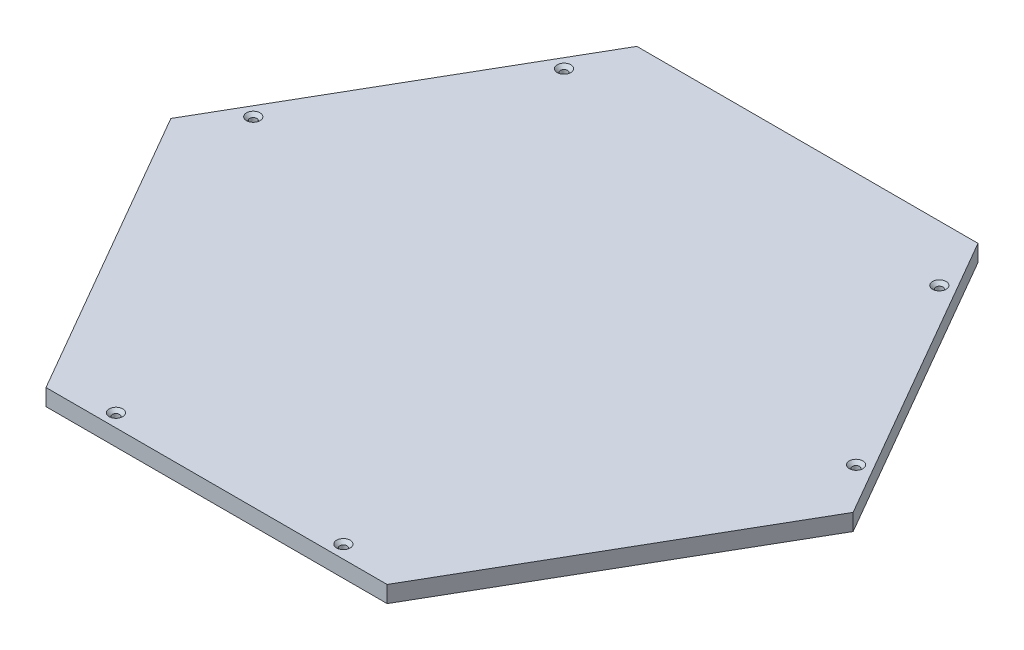
SolidWorks part; units mm, degrees
ref_plane "Front Plane" through (0, 0, 0) normal (0, 0, 1) x (1, 0, 0)
ref_plane "Top Plane" through (0, 0, 0) normal (0, 1, 0) x (1, 0, 0)
ref_plane "Right Plane" through (0, 0, 0) normal (1, 0, 0) x (0, 0, -1)
sketch "Sketch1" plane through (0, 484.3134, 0) normal (0, 1, 0) x (1, 0, 0)
  line L0 (745.0585, -1508.4785) -> (535.0585, -1872.2091) construction
  line L1 (1096.7234, -1803.3391) -> (966.2477, -1577.3485)
  line L2 (966.2477, -1577.3485) -> (705.2963, -1577.3485)
  line L3 (705.2963, -1577.3485) -> (574.8206, -1803.3391)
  line L4 (574.8206, -1803.3391) -> (705.2963, -2029.3296)
  line L5 (705.2963, -2029.3296) -> (966.2477, -2029.3296)
  line L6 (966.2477, -2029.3296) -> (1096.7234, -1803.3391)
  line L7 (1136.4856, -1872.2091) -> (926.4856, -1508.4785) construction
  line L8 (625.772, -2029.3296) -> (1045.772, -2029.3296) construction
  circle A0 centre (835.772, -1803.3391) radius 225.9905 construction
extrude "Boss-Extrude1" add sketch "Sketch1" along normal blind 12.7
sketch "Sketch2" plane through (0, 497.0134, 0) normal (0, 1, 0) x (1, 0, 0)
  line L0 (835.772, -1577.3485) -> (835.772, -1724.1646)
  line L1 (966.2477, -1577.3485) -> (705.2963, -1577.3485) construction
  line L2 (1031.4856, -1916.3343) -> (962.1709, -1876.3155)
  line L3 (966.2477, -2029.3296) -> (1096.7234, -1803.3391) construction
  line L4 (640.0585, -1916.3343) -> (702.4259, -1880.3243)
  line L5 (574.8206, -1803.3391) -> (705.2963, -2029.3296) construction
  line L6 (640.0585, -1690.3438) -> (648.7187, -1695.3438)
  line L7 (705.2963, -1577.3485) -> (574.8206, -1803.3391) construction
  line L8 (605.2187, -1770.688) -> (692.2187, -1619.9996)
  line L9 (574.8206, -1803.3391) -> (596.5496, -1815.8843)
  line L10 (1066.3253, -1770.688) -> (979.3253, -1619.9996)
  line L11 (1031.4856, -1690.3438) -> (1022.8253, -1695.3438)
  line L12 (748.7776, -2019.3237) -> (922.7776, -2019.3144)
  line L13 (835.7781, -2029.3191) -> (835.7776, -2019.3191)
  point P30 (605.2187, -1770.688)
  point P31 (692.2187, -1619.9996)
  point P32 (979.3253, -1619.9996)
  point P33 (1066.3253, -1770.688)
  point P34 (922.7776, -2019.3144)
  point P35 (748.7776, -2019.3237)
  dimension "D1" = 174
  dimension "D2" = 10
hole_wizard "CSK for M5 Flat Head Machine Screw1" positions "Sketch6" profile "Sketch5" countersink size "M5" standard "ANSI Metric" end condition up to next
sketch "Sketch6" plane through (0, 497.0134, 0) normal (0, 1, 0) x (1, 0, 0)
  line L0 (640.0585, -1690.3438) -> (648.7187, -1695.3438) construction
  line L1 (640.0585, -1916.3343) -> (702.4259, -1880.3243) construction
  line L2 (1031.4856, -1916.3343) -> (962.1709, -1876.3155) construction
  line L3 (835.772, -1577.3485) -> (835.772, -1724.1646) construction
  line L4 (835.7781, -2029.3191) -> (835.7776, -2019.3191) construction
  line L5 (748.7776, -2019.3237) -> (922.7776, -2019.3144) construction
  line L6 (1031.4856, -1690.3438) -> (1022.8253, -1695.3438) construction
  line L7 (1066.3253, -1770.688) -> (979.3253, -1619.9996) construction
  line L8 (574.8206, -1803.3391) -> (596.5496, -1815.8843) construction
  line L9 (605.2187, -1770.688) -> (692.2187, -1619.9996) construction
  line L10 (640.0585, -1690.3438) -> (648.7187, -1695.3438) construction
  line L11 (640.0585, -1916.3343) -> (702.4259, -1880.3243) construction
  line L12 (1031.4856, -1916.3343) -> (962.1709, -1876.3155) construction
  line L13 (835.772, -1577.3485) -> (835.772, -1724.1646) construction
  line L14 (835.7781, -2029.3191) -> (835.7776, -2019.3191) construction
  line L15 (748.7776, -2019.3237) -> (922.7776, -2019.3144) construction
  line L16 (1031.4856, -1690.3438) -> (1022.8253, -1695.3438) construction
  line L17 (1066.3253, -1770.688) -> (979.3253, -1619.9996) construction
  line L18 (574.8206, -1803.3391) -> (596.5496, -1815.8843) construction
  line L19 (605.2187, -1770.688) -> (692.2187, -1619.9996) construction
  point P0 (605.2187, -1770.688)
  point P2 (692.2187, -1619.9996)
  point P4 (979.3253, -1619.9996)
  point P6 (1066.3253, -1770.688)
  point P8 (748.7776, -2019.3237)
  point P10 (922.7776, -2019.3144)
sketch "Sketch5" plane through (605.2187, 497.0134, 1770.688) normal (1, 0, 0) x (0, 0, 1)
  line L0 (0, 0) -> (0, 12.7)
  line L1 (0, 12.7) -> (2.75, 12.7)
  line L2 (2.75, 12.7) -> (2.75, 2.45)
  line L3 (2.75, 2.45) -> (5.2, 0)
  line L5 (5.2, 0) -> (0, 0)
  line L6 (-2.75, 2.45) -> (-5.2, 0) construction
  line L11 (0, -6.35) -> (0, 107.95) construction
  dimension "Thru Hole Dia." = 5.5
  dimension "Thru Hole Depth" = 12.7
  dimension "Near C'Sink Dia." = 10.4
  dimension "Near C'Sink Angle" = 90
sketch "Sketch7" plane through (0, 0, 0) normal (0, 1, 0) x (1, 0, 0)
  line L1 (1284.0363, -1558.6414) -> (1314.0363, -1558.6414)
  line L2 (1284.0363, -1558.6414) -> (1284.0363, -2010.6344)
  line L3 (1284.0363, -2010.6344) -> (1314.0363, -2010.6344)
  line L4 (1314.0363, -1558.6414) -> (1314.0363, -2010.6344)
  line L5 (1432.0991, -1558.6414) -> (1462.0991, -1558.6414)
  line L6 (1432.0991, -1558.6414) -> (1432.0991, -2011.0789)
  line L7 (1432.0991, -2011.0789) -> (1462.0991, -2011.0789)
  line L8 (1462.0991, -1558.6414) -> (1462.0991, -2011.0789)
  line L9 (1573.8804, -1558.6414) -> (1603.8804, -1558.6414)
  line L10 (1573.8804, -1558.6414) -> (1573.8804, -2010.2852)
  line L11 (1573.8804, -2010.2852) -> (1603.8804, -2010.2852)
  line L12 (1603.8804, -1558.6414) -> (1603.8804, -2010.2852)
  line L13 (1700.7101, -1558.6414) -> (1730.7101, -1558.6414)
  line L14 (1700.7101, -1558.6414) -> (1700.7101, -2011.0789)
  line L15 (1700.7101, -2011.0789) -> (1730.7101, -2011.0789)
  line L16 (1730.7101, -1558.6414) -> (1730.7101, -2011.0789)
  dimension "D1" = 451.993
  dimension "D2" = 30
  dimension "D3" = 30
  dimension "D4" = 452.4375
  dimension "D5" = 30
  dimension "D6" = 451.6438
  dimension "D7" = 30
  dimension "D8" = 452.4375
